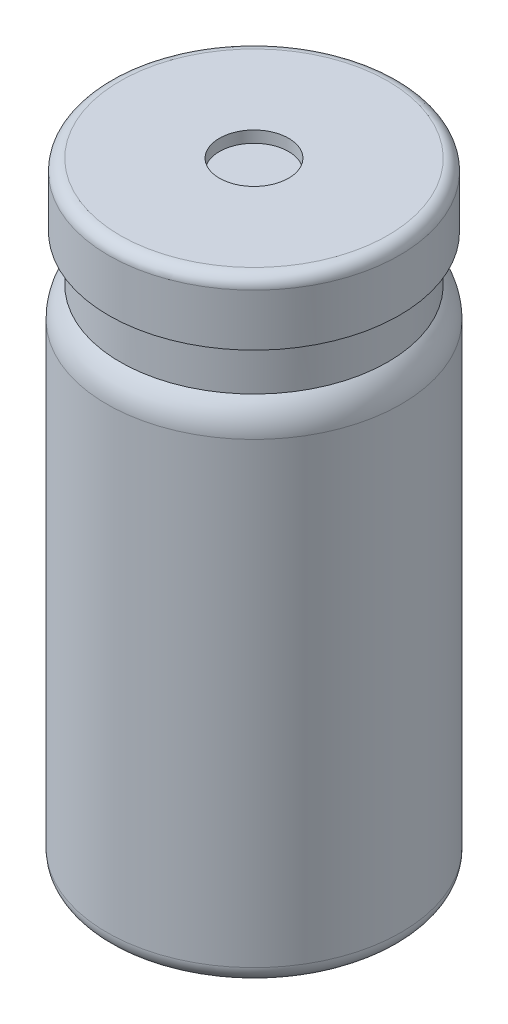
SolidWorks part; units mm, degrees
material "Glass"
ref_plane "Front Plane" through (0, 0, 0) normal (0, 0, 1) x (1, 0, 0)
ref_plane "Top Plane" through (0, 0, 0) normal (0, 1, 0) x (1, 0, 0)
ref_plane "Right Plane" through (0, 0, 0) normal (1, 0, 0) x (0, 0, -1)
sketch "Sketch1" plane through (0, 0, 0) normal (0, 0, 1) x (1, 0, 0)
  line L0 (0, 0) -> (-12.745, 0)
  line L1 (-12.745, 0) -> (-12.745, 43.73)
  line L2 (-12.745, 43.73) -> (-11.595, 43.73)
  line L3 (-11.595, 43.73) -> (-11.595, 51.23)
  line L4 (-11.595, 51.23) -> (0, 51.23)
  line L5 (0, 51.23) -> (0, 0)
  dimension "D1" = 12.745
  dimension "D2" = 1.15
  dimension "D3" = 7.5
  dimension "D4" = 51.23
revolve "Revolve1" add sketch "Sketch1" angle 360 about L5
fillet "Fillet1" radius 3.5 1 edges at (-12.745, 43.73, 0)
fillet "Fillet2" radius 1.5 1 edges at (-12.745, 0, 0)
sketch "Sketch2" plane through (0, 0, 0) normal (1, 0, 0) x (0, 0, -1)
  line L13 (0, 51.23) -> (0, 34.7514) construction
  line L15 (11.595, 51.23) -> (-11.595, 51.23) construction
  line L16 (3, 52.23) -> (11.595, 52.23)
  line L17 (11.595, 52.23) -> (11.595, 47.73)
  line L18 (11.595, 43.73) -> (11.595, 51.23) construction
  line L19 (-11.595, 43.73) -> (11.595, 43.73) construction
  line L20 (3, 53.23) -> (12.595, 53.23)
  line L21 (12.595, 53.23) -> (12.595, 47.73)
  line L22 (3, 53.23) -> (3, 52.23)
  line L23 (11.595, 47.73) -> (12.595, 47.73)
  dimension "D1" = 3
  dimension "D2" = 4
  dimension "D3" = 1
  dimension "D4" = 1
revolve "Revolve2" add sketch "Sketch2" angle 360 about L13
fillet "Fillet3" radius 1 1 edges at (0, 53.23, 12.595)
